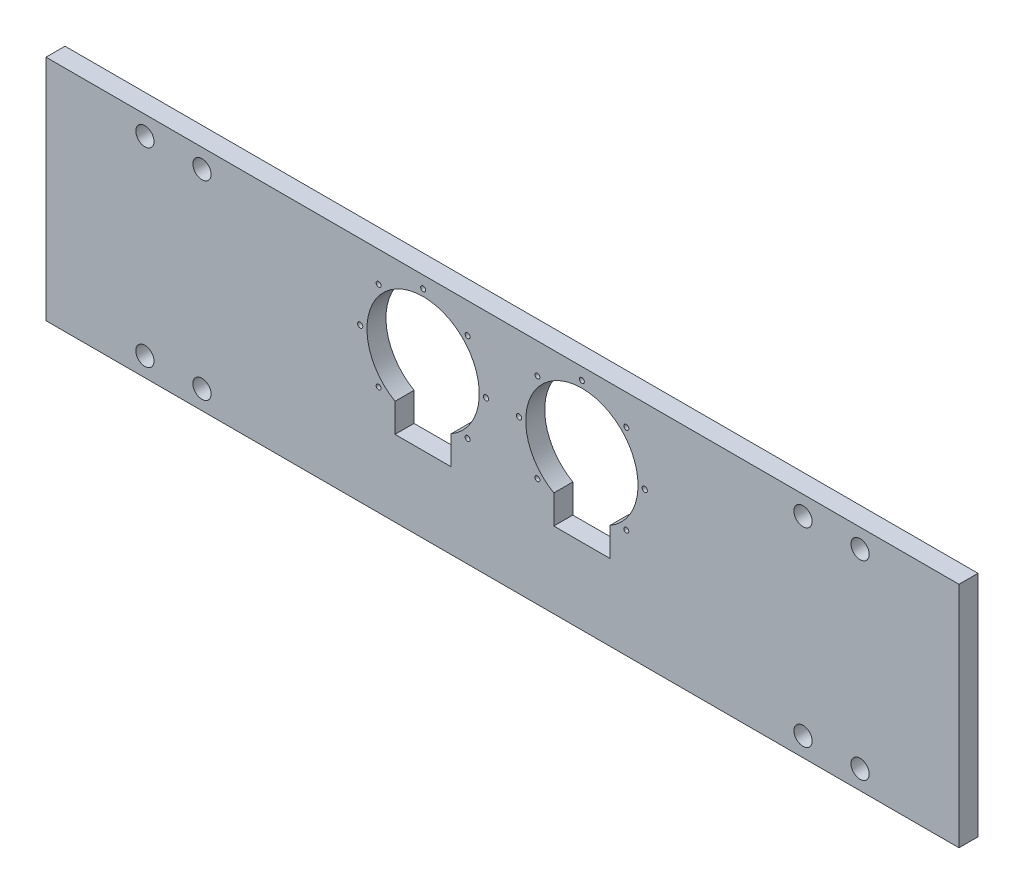
SolidWorks part; units mm, degrees
material "1060 Alloy"
ref_plane "Front Plane" through (0, 0, 0) normal (0, 0, 1) x (1, 0, 0)
ref_plane "Top Plane" through (0, 0, 0) normal (0, 1, 0) x (1, 0, 0)
ref_plane "Right Plane" through (0, 0, 0) normal (1, 0, 0) x (0, 0, -1)
sketch "Sketch1" plane through (0, 0, 0) normal (0, 0, 1) x (1, 0, 0)
  line L0 (-304.8, 0) -> (304.8, 0) construction
  line L1 (-304.8, 76.2) -> (304.8, 76.2)
  line L2 (-304.8, 76.2) -> (-304.8, -76.2)
  line L3 (-304.8, -76.2) -> (304.8, -76.2)
  line L4 (304.8, 76.2) -> (304.8, -76.2)
  line L7 (0, 76.2) -> (0, -76.2) construction
  line L8 (53, 26.2) -> (53, -11.3) construction
  line L9 (53, 26.2) -> (34.25, -6.276) construction
  line L10 (53, 26.2) -> (71.75, -6.276) construction
  line L11 (34.25, -6.276) -> (34.25, -25.4)
  line L12 (71.75, -6.276) -> (71.75, -25.4)
  line L13 (71.75, -25.4) -> (34.25, -25.4)
  line L14 (238.76, 76.2) -> (238.76, -76.2) construction
  line L15 (200.66, 76.2) -> (200.66, -76.2) construction
  line L16 (-34.25, -6.276) -> (-34.25, -25.4)
  line L17 (-71.75, -25.4) -> (-34.25, -25.4)
  line L18 (-71.75, -6.276) -> (-71.75, -25.4)
  arc A6 (71.75, -6.276) -> (34.25, -6.276) centre (53, 26.2) ccw
  circle A7 centre (53, 26.2) radius 42 construction
  circle A9 centre (82.6985, 55.8985) radius 1.6497
  circle A10 centre (95, 26.2) radius 1.746
  circle A11 centre (82.6985, -3.4985) radius 1.6497
  circle A13 centre (23.3015, -3.4985) radius 1.6497
  circle A14 centre (11, 26.2) radius 1.746
  circle A15 centre (23.3015, 55.8985) radius 1.6497
  circle A16 centre (-53, 68.2) radius 1.6497
  circle A17 centre (238.76, 63.5) radius 6.096
  circle A18 centre (200.66, 63.5) radius 6.096
  circle A19 centre (238.76, -63.5) radius 6.096
  circle A20 centre (200.66, -63.5) radius 6.096
  circle A21 centre (-82.6985, -3.4985) radius 1.6497
  circle A22 centre (-95, 26.2) radius 1.746
  circle A23 centre (-82.6985, 55.8985) radius 1.6497
  circle A25 centre (-23.3015, 55.8985) radius 1.6497
  circle A26 centre (-11, 26.2) radius 1.746
  circle A27 centre (-23.3015, -3.4985) radius 1.6497
  arc A28 (-71.75, -6.276) -> (-34.25, -6.276) centre (-53, 26.2) cw
  circle A29 centre (-238.76, 63.5) radius 6.096
  circle A30 centre (-200.66, 63.5) radius 6.096
  circle A31 centre (-200.66, -63.5) radius 6.096
  circle A32 centre (-238.76, -63.5) radius 6.096
  circle A33 centre (53, 68.2) radius 1.6497
  point P0 (0, 0)
  point P32 (53, 26.2)
  dimension "D6" = 75
  dimension "D7" = 84
  dimension "D15" = 12.192
  dimension "D17" = 12.192
  dimension "D8" = 3.2995
  dimension "D3" = 3.492
  dimension "D1" = 609.6
  dimension "D2" = 152.4
  dimension "D4" = 53
  dimension "D5" = 50
  dimension "D10" = 30
  dimension "D11" = 30
  dimension "D12" = 50.8
  dimension "D13" = 66.04
  dimension "D14" = 38.1
  dimension "D16" = 12.7
  dimension "D18" = 12.7
extrude "Boss-Extrude1" add sketch "Sketch1" along normal blind 12.7
equation "\"bplate_length\"= 24in"
equation "\"bplate_height\"= 6in"
equation "\"bplate_thickness\"= 0.5in"
equation "\"motor_diameter\"= 96 / 25.4in"
equation "\"motor_clearance\"= 5 / 25.4in"
equation "\"motor_mount_hole_pattern_dia\"= 84 / 25.4in"
equation "\"motor_mount_hole_dia\"= 4 / 25.4in"
equation "\"motor_cx\"= \"motor_clearance\" + \"motor_diameter\" / 2in"
equation "\"motor_cy_top\"= \"motor_mount_hole_pattern_dia\" / 2 + \"motor_mount_hole_dia\" * 2in"
equation "\"D1@Sketch1\"=\"bplate_length\""
equation "\"D2@Sketch1\"=\"bplate_height\""
equation "\"motor_driver_cover_dia\"= 75 / 25.4in"
equation "\"D4@Sketch1\"=\"motor_cx\""
equation "\"motor_driver_cutout_clearance\"= 60deg"
equation "\"wire_cutout_clearance\"= 2in"
equation "\"connector_plate_thickness\"= 1in"
equation "\"connector_plate_hole_diameter\"= 0.5in"
equation "\"connector_plate_hole_depth\"= 1in"
equation "\"coonector_first_hole_offset\"= 1.6in"
equation "\"D14@Sketch1\"=1.5"
equation "\"D13@Sketch1\"=\"coonector_first_hole_offset\"+1in"
equation "\"D12@Sketch1\"=\"wire_cutout_clearance\""
equation "\"D16@Sketch1\"=\"connector_plate_thickness\"/2"
equation "\"D18@Sketch1\"=\"connector_plate_thickness\"/2"
equation "\"D15@Sketch1\"=\"connector_plate_hole_diameter\"- 0.02"
equation "\"D17@Sketch1\"=\"connector_plate_hole_diameter\"-0.02"
equation "\"D6@Sketch1\"=\"motor_driver_cover_dia\""
equation "\"D7@Sketch1\"=\"motor_mount_hole_pattern_dia\""
equation "\"D3@Sketch1\"=\"motor_mount_hole_dia\" - 0.02"
